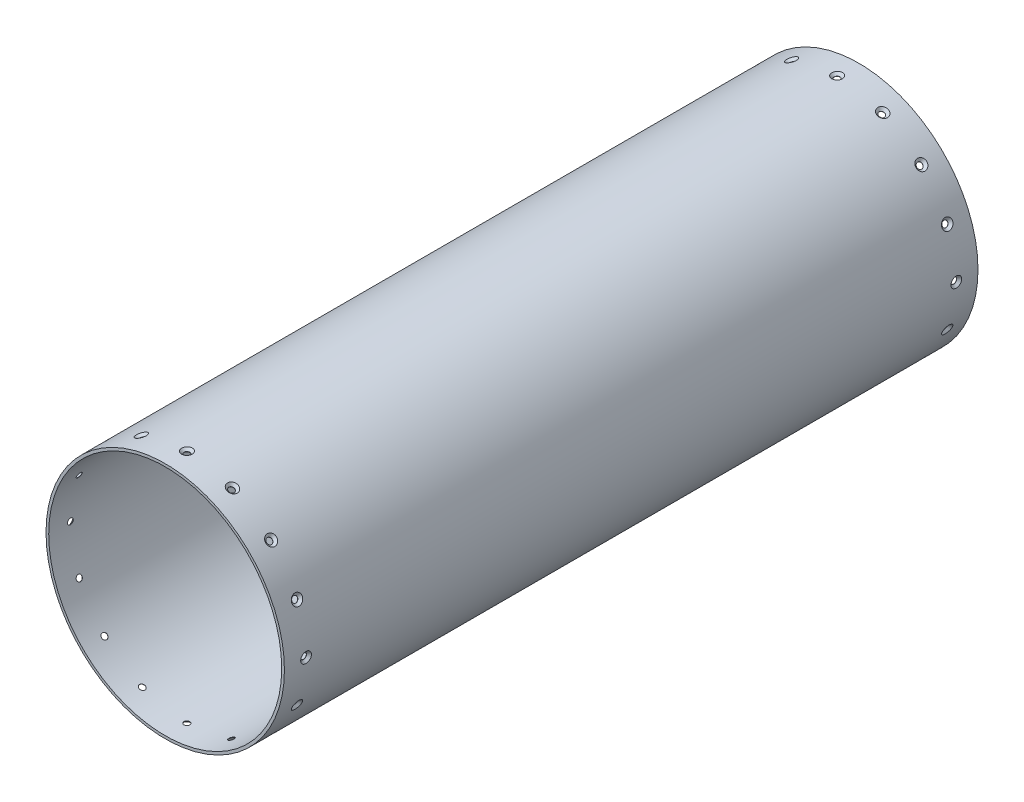
SolidWorks part; units mm, degrees
material "6061-T6 (SS)"
ref_plane "Front Plane" through (0, 0, 0) normal (0, 0, 1) x (1, 0, 0)
ref_plane "Top Plane" through (0, 0, 0) normal (0, 1, 0) x (1, 0, 0)
ref_plane "Right Plane" through (0, 0, 0) normal (1, 0, 0) x (0, 0, -1)
sketch "Sketch1" plane through (0, 0, 0) normal (0, 0, 1) x (1, 0, 0)
  circle A0 centre (0, 0) radius 69.85
  circle A1 centre (0, 0) radius 68.2625
  dimension "D1" = 139.7
  dimension "D2" = 1.5875
extrude "Extrude1" add sketch "Sketch1" along normal blind 406.4
ref_plane "Plane1" through (0, 0, 12.7) normal (0, 0, -1) x (-1, 0, 0)
sketch "Sketch2" plane through (0, 0, 12.7) normal (0, 0, -1) x (-1, 0, 0)
  line L0 (0, 0) -> (0, -69.85) construction
  circle A0 centre (0, 0) radius 69.85 construction
ref_plane "Plane2" through (0, -69.85, 12.7) normal (0, -1, 0) x (1, 0, 0)
hole_wizard "CSK for M3 Flat Head Machine Screw1" positions "Sketch5" profile "Sketch4" countersink size "M3" standard "Ansi Metric" end condition through all
sketch "Sketch5" plane through (0, -69.85, 12.7) normal (0, -1, 0) x (1, 0, 0)
  point P2 (0, 0)
sketch "Sketch4" plane through (0, -69.85, 12.7) normal (1, 0, 0) x (0, 0, -1)
  line L0 (0, 0) -> (0, 161.1134)
  line L1 (0, 161.1134) -> (1.7, 161.1134)
  line L2 (1.7, 161.1134) -> (1.7, 1.45)
  line L3 (1.7, 1.45) -> (3.15, 0)
  line L5 (3.15, 0) -> (0, 0)
  line L6 (-1.7, 1.45) -> (-3.15, 0) construction
  line L11 (0, -6.35) -> (0, 107.95) construction
  dimension "Thru Hole Dia." = 3.4
  dimension "Thru Hole Depth" = 161.1134
  dimension "Near C'Sink Dia." = 6.3
  dimension "Near C'Sink Angle" = 90
pattern_circular "CirPattern1" count 16 over 360 about axis through (0, 0, 406.4) along (0, 0, -1) of "CSK for M3 Flat Head Machine Screw1"
ref_plane "Plane3" through (0, 0, 395.2875) normal (0, 0, 1) x (1, 0, 0)
ref_plane "Plane5" through (0, 0, 0) normal (0.8315, 0.5556, 0) x (-0.5556, 0.8315, 0)
ref_plane "Plane7" through (0, 0, 0) normal (0.5556, -0.8315, 0) x (0.8315, 0.5556, 0)
ref_plane "Plane9" through (0, 0, 0) normal (-0.1951, -0.9808, 0) x (0.9808, -0.1951, 0)
sketch "Sketch7" plane through (0, 0, 406.4) normal (0, 0, 1) x (1, 0, 0)
  circle A0 centre (0, 0) radius 69.85 construction
  point P0 (69.85, 0)
ref_plane "Plane8" through (-68.5079, 13.6271, 203.2) normal (-0.9808, 0.1951, 0) x (0.1951, 0.9808, 0)
sketch "Sketch8" plane through (-68.5079, 13.6271, 203.2) normal (-0.9808, 0.1951, 0) x (0.1951, 0.9808, 0)
  line L0 (0, -425.45) -> (0, -414.3248) construction
pattern_linear "LPattern1" count 2 spacing 381 along (0, 0, 1) of "CirPattern1"
